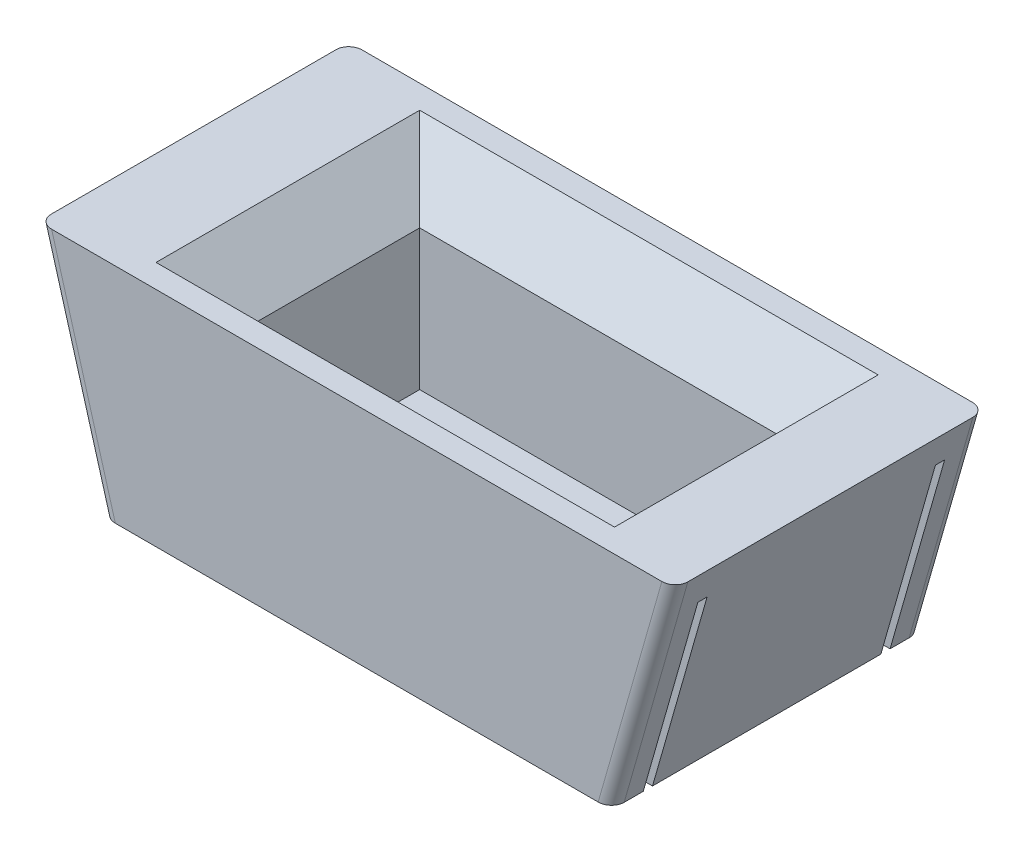
SolidWorks part; units mm, degrees
ref_plane "Front" through (0, 0, 0) normal (0, 0, 1) x (1, 0, 0)
ref_plane "Top" through (0, 0, 0) normal (0, 1, 0) x (1, 0, 0)
ref_plane "Right" through (0, 0, 0) normal (1, 0, 0) x (0, 0, -1)
sketch "Sketch1" plane through (0, 0, 0) normal (0, 1, 0) x (1, 0, 0)
  line L1 (-63.5, -24.6126) -> (63.5, -24.6126)
  line L2 (-63.5, -24.6126) -> (-63.5, 24.6126)
  line L3 (-63.5, 24.6126) -> (63.5, 24.6126)
  line L4 (63.5, -24.6126) -> (63.5, 24.6126)
  line L5 (0, 24.6126) -> (0, -24.6126) construction
  line L6 (-63.5, 0) -> (63.5, 0) construction
  line L7 (-63.5, -22.7711) -> (63.5, -22.7711)
  line L8 (-63.5, -22.7711) -> (-63.5, 22.7711)
  line L9 (-63.5, 22.7711) -> (63.5, 22.7711)
  line L10 (63.5, -22.7711) -> (63.5, 22.7711)
  line L11 (0, 22.7711) -> (0, -22.7711) construction
  line L12 (-63.5, 0) -> (63.5, 0) construction
  line L13 (-63.5, -30.9626) -> (63.5, -30.9626)
  line L14 (-63.5, -30.9626) -> (-63.5, 30.9626)
  line L15 (-63.5, 30.9626) -> (63.5, 30.9626)
  line L16 (63.5, -30.9626) -> (63.5, 30.9626)
  line L17 (0, 30.9626) -> (0, -30.9626) construction
  line L18 (-63.5, 0) -> (63.5, 0) construction
  point P0 (0, 0)
  point P4 (0, 0)
  point P8 (0, 0)
  dimension "D1" = 49.2252
  dimension "D2" = 127
  dimension "D3" = 1.8415
  dimension "D4" = 6.35
extrude "Boss-Extrude1" add sketch "Sketch1" along normal blind 44.45 contours L3 L16 L15 L14 | L13 L16 L1 L14 | L3 L4 L1 L2 region at (0, 0, 27.7876) region at (0, 0, -27.7876)
extrude "Cut-Extrude2" cut sketch "Sketch1<3>" along normal blind 38.1 contours L2 L9 L4 L3 | L7 L2 L1 L4 region at (0, 0, 23.6919) region at (0, 0, -23.6919)
sketch "Sketch1<3>" plane through (0, 0, 0) normal (0, 1, 0) x (1, 0, 0) same geometry as "Sketch1"
sketch "Sketch2" plane through (0, 44.45, 0) normal (0, 1, 0) x (1, 0, 0)
  line L0 (63.5, -30.9626) -> (63.5, 30.9626) construction
  line L1 (-34.544, -16.129) -> (36.576, -16.129)
  line L3 (-34.544, 16.129) -> (36.576, 16.129)
  line L4 (36.576, -16.129) -> (36.576, 16.129)
  line L5 (1.016, 16.129) -> (1.016, -16.129) construction
  line L6 (-34.544, 0) -> (36.576, 0) construction
  line L11 (1.016, 12.7) -> (1.016, -12.7) construction
  line L12 (-20.32, 0) -> (20.32, 0) construction
  line L13 (-5.2166, -11.5914) -> (30.226, -11.5914)
  line L14 (-5.2166, -11.5914) -> (-5.2166, 11.5914)
  line L15 (-5.2166, 11.5914) -> (30.226, 11.5914)
  line L16 (30.226, -11.5914) -> (30.226, 11.5914)
  line L17 (12.5047, 11.5914) -> (12.5047, -11.5914) construction
  line L18 (-5.2166, 0) -> (30.226, 0) construction
  line L19 (-34.544, 16.129) -> (-34.544, -16.129)
  line L20 (-63.5, -30.9626) -> (63.5, -30.9626) construction
  point P0 (0, 0)
  point P4 (1.016, 0)
  point P5 (12.5047, 0)
  dimension "D1" = 32.258
  dimension "D3" = 6.35
  dimension "D4" = 35.4426
  dimension "D5" = 23.1828
  dimension "D6" = 71.12
  dimension "D7" = 26.924
  dimension "D8" = 14.8336
extrude "Cut-Extrude3" cut sketch "Sketch2" against normal blind 38.1
chamfer "Chamfer2" distance 10.16 angle 45 4 edges at (1.016, 44.45, 16.129) (1.016, 44.45, -16.129) (36.576, 44.45, 0) (-34.544, 44.45, 0)
sketch "Sketch7" plane through (0, 0, 30.9626) normal (0, 0, 1) x (1, 0, 0)
  line L0 (-63.5, 44.45) -> (-63.5, 0)
  line L1 (-63.5, 44.45) -> (63.5, 44.45) construction
  line L2 (-63.5, 44.45) -> (-63.5, 0) construction
  line L3 (-63.5, 0) -> (63.5, 0) construction
  line L4 (63.5, 44.45) -> (63.5, 0) construction
  line L7 (-63.5, 0) -> (-50.7955, 0)
  line L8 (-50.7955, 0) -> (-63.5, 44.45)
  line L9 (0, 0) -> (0, 44.45)
  line L10 (63.5, 0) -> (50.7955, 0)
  line L11 (63.5, 44.45) -> (63.5, 0)
  line L12 (50.7955, 0) -> (63.5, 44.45)
  point P4 (0, 22.225)
  point P12 (0, 22.225)
  line M13 (-63.5, 0) -> (63.5, 0)
  line M18 (63.5, 0) -> (63.5, 44.45)
  line M19 (-63.5, 44.45) -> (-63.5, 0)
extrude "Cut-Extrude5" cut sketch "Sketch7" against normal through all contours L8 M13 M19 | L12 M13 M18 region at (-59.2652, 14.8167, 30.9626) region at (59.2652, 14.8167, 30.9626)
fillet "Fillet3" radius 2.54 4 edges at (-57.1477, 22.225, 30.9626) (-57.1477, 22.225, -30.9626) (57.1477, 22.225, -30.9626) (57.1477, 22.225, 30.9626)
extrude "Cut-Extrude6" cut sketch "Sketch2<3>" against normal through all contours L15 L16 L13 L14
sketch "Sketch2<3>" plane through (0, 44.45, 0) normal (0, 1, 0) x (1, 0, 0) same geometry as "Sketch2"
chamfer "Chamfer3" distance 2.54 angle 45 4 edges at (12.5047, 0, 11.5914) (-5.2166, 0, 0) (30.226, 0, 0) (12.5047, 0, -11.5914)
